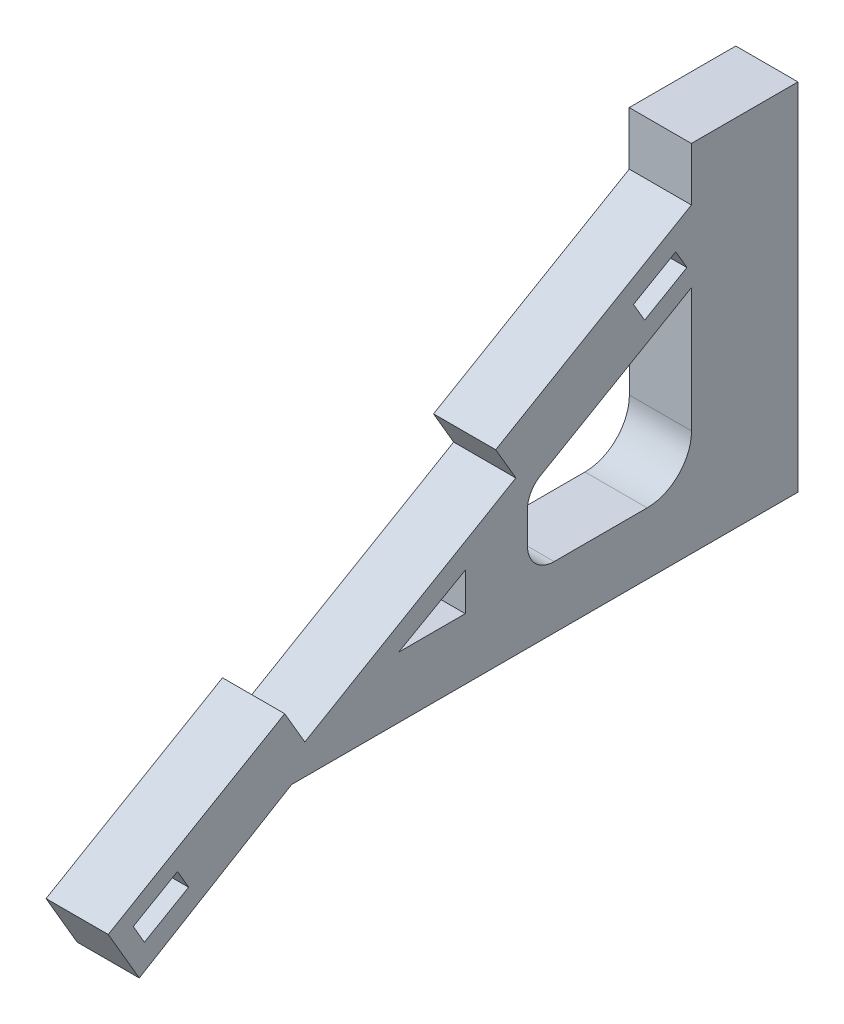
SolidWorks part; units mm, degrees
ref_plane "Front Plane" through (0, 0, 0) normal (0, 0, 1) x (1, 0, 0)
ref_plane "Top Plane" through (0, 0, 0) normal (0, 1, 0) x (1, 0, 0)
ref_plane "Right Plane" through (0, 0, 0) normal (1, 0, 0) x (0, 0, -1)
sketch "Sketch1" plane through (0, 0, 0) normal (1, 0, 0) x (0, 0, -1)
  line L0 (-21.7856, -17.3779) -> (35.2144, -17.3779)
  line L5 (35.2144, -17.3779) -> (35.2144, 22.6221)
  line L6 (35.2144, 22.6221) -> (23.2144, 22.6221)
  line L7 (23.2144, 22.6221) -> (23.2144, 16.6221)
  line L8 (1.1877, 3.774) -> (23.2144, 16.6221)
  line L9 (1.1877, 3.774) -> (3.455, -0.1131)
  line L10 (3.455, -0.1131) -> (-20.2993, -13.9689)
  line L11 (-20.2993, -13.9689) -> (-22.5666, -10.0818)
  line L12 (-22.5666, -10.0818) -> (-42.4338, -21.6704)
  line L13 (-42.4338, -21.6704) -> (-38.9371, -27.6651)
  line L14 (-38.9371, -27.6651) -> (-21.7856, -17.3779)
  line L15 (23.2341, 8.5696) -> (23.2341, -10.4179)
  line L19 (-39.6139, -22.3046) -> (-34.6345, -19.4291)
  line L20 (-34.6345, -19.4291) -> (-33.3843, -21.5941)
  line L21 (-33.3843, -21.5941) -> (-38.3637, -24.4695)
  line L22 (-38.3637, -24.4695) -> (-39.6139, -22.3046)
  line L23 (-9.7355, -10.4979) -> (-2.2353, -10.4979)
  line L24 (-2.2353, -10.4979) -> (-2.2353, -6.2484)
  line L25 (-2.2353, -6.2484) -> (-9.7355, -10.4979)
  line L26 (16.6994, 10.1829) -> (17.9518, 8.0192)
  line L27 (17.9518, 8.0192) -> (22.7119, 10.7746)
  line L28 (22.7119, 10.7746) -> (21.4594, 12.9383)
  line L29 (21.4594, 12.9383) -> (16.6994, 10.1829)
  line L31 (4.7647, -1.3999) -> (6.0116, -1.3999)
  line L32 (4.7647, -1.3999) -> (4.7647, -10.4179)
  line L33 (4.7647, -10.4179) -> (23.2341, -10.4179)
  line L36 (6.0116, -1.3999) -> (23.2341, 8.5696)
  dimension "D1" = 57
  dimension "D2" = 40
  dimension "D3" = 12
  dimension "D4" = 25.5
  dimension "D5" = 6
  dimension "D6" = 27.5
  dimension "D7" = 4.5
  dimension "D8" = 4.5
  dimension "D9" = 23
  dimension "D10" = 6.94
  dimension "D11" = 20
  dimension "D12" = 5.75
  dimension "D13" = 2.5
  dimension "D14" = 0.25
  dimension "D15" = 6.88
  dimension "D16" = 6.96
  dimension "D17" = 7
  dimension "D18" = 0.72
  dimension "D19" = 0.19
  dimension "D20" = 2.17
extrude "Boss-Extrude1" add sketch "Sketch1" against normal blind 7
fillet "Fillet1" radius 3 2 edges at (-3.5, -10.4179, -4.7647) (-3.5, -1.3999, -4.7647)
fillet "Fillet2" radius 5 1 edges at (-3.5, -10.4179, -23.2341)
